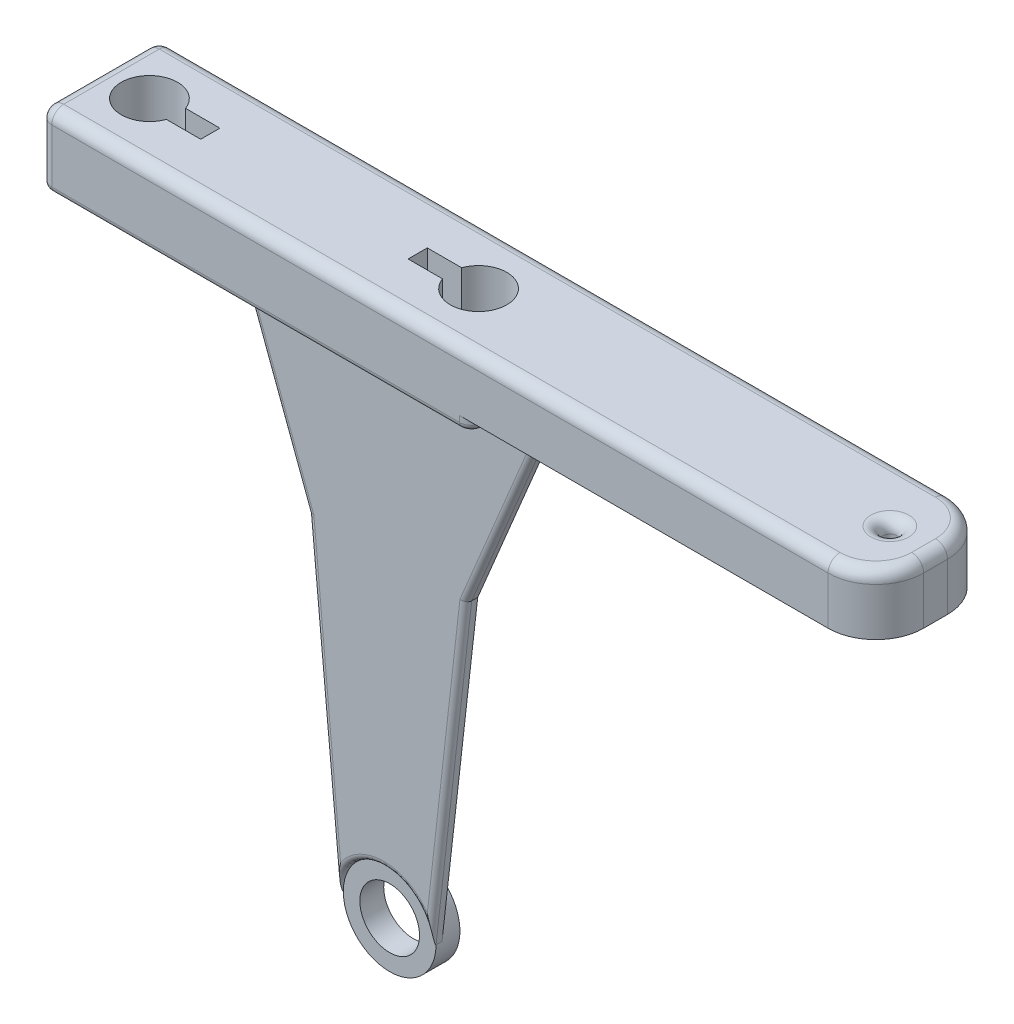
SolidWorks part; units mm, degrees
ref_plane "Front Plane" through (0, 0, 0) normal (0, 0, 1) x (1, 0, 0)
ref_plane "Top Plane" through (0, 0, 0) normal (0, 1, 0) x (1, 0, 0)
ref_plane "Right Plane" through (0, 0, 0) normal (1, 0, 0) x (0, 0, -1)
sketch "Sketch1" plane through (0, 0, 0) normal (0, 1, 0) x (1, 0, 0)
  line L0 (-104.9541, -22.6191) -> (-100.3423, -22.6191) construction
  line L1 (-102.4141, -35.3191) -> (62.6859, -35.3191)
  line L2 (-104.9541, -32.7791) -> (-104.9541, -12.4591)
  line L3 (-102.4141, -9.9191) -> (62.6859, -9.9191)
  line L4 (72.8459, -25.1591) -> (72.8459, -20.0791)
  line L5 (-104.9541, -35.3191) -> (72.8459, -9.9191) construction
  line L6 (-104.9541, -9.9191) -> (72.8459, -35.3191) construction
  line L7 (-88.3423, -22.6191) -> (-81.3956, -22.6191) construction
  line L8 (-88.7, -20.5785) -> (-81.3956, -20.5785)
  line L9 (-81.3956, -20.5785) -> (-81.3956, -24.6597)
  line L10 (-88.3423, -22.6191) -> (-30.3423, -22.6191) construction
  line L11 (-59.3423, -26.1601) -> (-59.3423, -19.0782) construction
  line L12 (-88.7, -24.6597) -> (-81.3956, -24.6597)
  line L13 (-29.9846, -24.6597) -> (-37.289, -24.6597)
  line L14 (-37.289, -20.5785) -> (-37.289, -24.6597)
  line L15 (-29.9846, -20.5785) -> (-37.289, -20.5785)
  arc A0 (-88.7, -20.5785) -> (-88.7, -24.6597) centre (-94.3423, -22.6191) ccw
  arc A1 (-102.4141, -35.3191) -> (-104.9541, -32.7791) centre (-102.4141, -32.7791) cw
  arc A2 (-104.9541, -12.4591) -> (-102.4141, -9.9191) centre (-102.4141, -12.4591) cw
  arc A3 (-30.0018, -24.6117) -> (-30.0018, -20.6266) centre (-24.3423, -22.6191) ccw
  circle A4 centre (63.1357, -22.6191) radius 1.5
  arc A5 (62.6859, -35.3191) -> (72.8459, -25.1591) centre (62.6859, -25.1591) ccw
  arc A6 (62.6859, -9.9191) -> (72.8459, -20.0791) centre (62.6859, -20.0791) cw
  point P0 (-16.0541, -22.6191)
  point P26 (-59.3423, -22.6191)
  dimension "D3" = 12
  dimension "D4" = 2.54
  dimension "D6" = 12
  dimension "D5" = 3
  dimension "D7" = 10.16
  dimension "D1" = 177.8
  dimension "D2" = 25.4
extrude "Boss-Extrude1" add sketch "Sketch1" along normal blind 12.7 contours A6 L3 A2 L2 A1 L1 A5 L4 A4 A3 L13 L14 L15 A0 L8 L9 L12 region at (-14.1072, 0, 22.6191)
chamfer "Chamfer1" distance 5.08 angle 37 1 edges at (63.1357, 0, 24.1191) first distance on face at (63.1357, 12.7, 24.1191)
fillet "Fillet1" radius 2.54 1 edges at (63.1357, 12.7, 24.1191)
fillet "Fillet2" radius 2.54 2 edges at (63.1357, 0, 27.9472) (63.1357, 5.08, 24.1191)
fillet "Fillet4" radius 2.54 8 edges at (-104.2101, 12.7, 10.6631) (-104.9541, 12.7, 22.6191) (-104.2101, 12.7, 34.5752) (-19.8641, 12.7, 35.3191) (69.8701, 12.7, 32.3433) (72.8459, 12.7, 22.6191) (69.8701, 12.7, 12.8949) (-19.8641, 12.7, 9.9191)
sketch "Sketch3" plane through (0, 0, 0) normal (0, -1, 0) x (1, 0, 0)
  line L1 (-102.4141, 35.3191) -> (62.6859, 35.3191) construction
  line L2 (-102.4141, 9.9191) -> (62.6859, 9.9191) construction
  line L4 (-104.9541, 12.4591) -> (-104.9541, 5.4999)
  line L5 (-104.9541, 12.4591) -> (-104.9541, 32.7791)
  line L6 (-102.4141, 2.9599) -> (-19.2443, 2.9599)
  line L7 (-102.4141, 35.3191) -> (-18.1922, 35.3191)
  line L8 (-17.4482, 3.7039) -> (-12.0651, 9.087)
  line L9 (-11.3297, 11.0919) -> (-13.1357, 32.9879)
  line L10 (-15.6671, 35.3191) -> (-18.1922, 35.3191)
  arc A0 (-13.1357, 32.9879) -> (-15.6671, 35.3191) centre (-15.6671, 32.7791) ccw
  arc A2 (-102.4141, 35.3191) -> (-104.9541, 32.7791) centre (-102.4141, 32.7791) ccw
  arc A3 (-12.0651, 9.087) -> (-11.3297, 11.0919) centre (-13.8612, 10.8831) ccw
  arc A4 (-19.2443, 2.9599) -> (-17.4482, 3.7039) centre (-19.2443, 5.4999) ccw
  arc A5 (-104.9541, 5.4999) -> (-102.4141, 2.9599) centre (-102.4141, 5.4999) ccw
  point P7 (-13.328, 35.3191)
  point P25 (-11.233, 9.9191)
  dimension "D1" = 2.54
extrude "Boss-Extrude2" add sketch "Sketch3" along normal blind 2.54
sketch "Sketch4" plane through (0, 0, 2.9599) normal (0, 0, -1) x (-1, 0, 0)
  line L0 (102.4141, 0) -> (102.4141, -2.54)
  line L1 (102.4141, -2.54) -> (79.0116, -65.1905)
  line L3 (62.9068, -132.3736) -> (62.9068, -122.5164) construction
  line L5 (53.0496, -132.3736) -> (45.4522, -65.1905)
  line L6 (72.764, -132.3736) -> (79.0116, -65.1905)
  line L8 (45.4522, -65.1905) -> (19.2443, -2.54)
  circle A1 centre (62.9068, -132.3736) radius 6.35
  circle A2 centre (62.9068, -132.3736) radius 9.8572
  line M1 (102.4141, 0) -> (19.2443, 0)
  line M2 (19.2443, 0) -> (19.2443, -2.54)
  line M3 (19.2443, -2.54) -> (102.4141, -2.54)
  line M4 (102.4141, -2.54) -> (102.4141, 0)
  dimension "D2" = 12.7
extrude "Boss-Extrude3" add sketch "Sketch4" along normal mid plane 2.54 separate body contours A2 L1 M3 | M4 M1 M2 M3 region at (-60.8292, -1.27, 2.9599) region at (-61.7635, -49.0425, 2.9599)
extrude "Boss-Extrude4" add sketch "Sketch4<3>" along normal blind 5.08 contours A2 A1 region at (-62.9068, -141.952, 2.9599)
sketch "Sketch4<3>" plane through (0, 0, 2.9599) normal (0, 0, -1) x (-1, 0, 0) same geometry as "Sketch4"
sketch "Sketch5" plane through (0, 0, 4.2299) normal (0, 0, 1) x (1, 0, 0)
  circle A0 centre (-62.9068, -132.3736) radius 123.825
  dimension "D1" = 247.65
fillet "Fillet10" radius 1.27 8 edges at (-75.8878, -98.782, 4.2299) (-90.7129, -33.8653, 4.2299) (-102.4141, -1.27, 4.2299) (-60.8292, 0, 4.2299) (-19.2443, -1.27, 4.2299) (-32.3483, -33.8653, 4.2299) (-49.2509, -98.782, 4.2299) (-62.9068, -122.5164, 4.2299)
fillet "Fillet11" radius 1.27 1 edges at (-60.8292, 0, 1.6899)
fillet "Fillet12" radius 1.27 2 edges at (-104.2101, 0, 10.6631) (-56.9626, 0, 9.9191)
fillet "Fillet13" radius 1.27 18 edges at (-18.2723, -2.54, 3.1533) (-60.8292, -2.54, 2.9599) (-104.2101, -2.54, 3.7039) (-104.9541, -2.54, 19.1395) (-104.2101, -2.54, 34.5752) (-59.0406, -2.54, 35.3191) (-13.9465, -2.54, 34.6475) (-12.2327, -2.54, 22.0399) (-11.4765, -2.54, 10.0084) (-104.9541, 0.1514, 10.4985) (-104.9541, 0, 7.5596) (-104.2101, 0, 3.7039) (-60.8292, 0, 2.9599) (-18.2723, 0, 3.1533) (-11.6168, 0.5477, 9.6937) (-14.7567, -2.54, 6.3955) (-12.2806, 0.0196, 8.8715) (-14.9756, 0, 6.1765)
